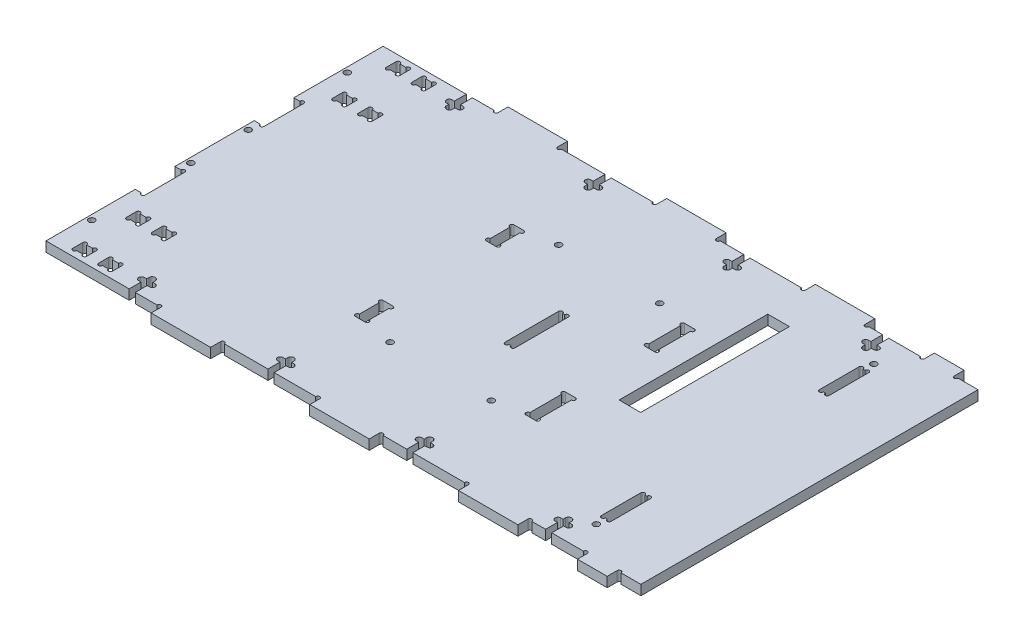
SolidWorks part; units mm, degrees
ref_plane "정면" through (0, 0, 0) normal (0, 0, 1) x (1, 0, 0)
ref_plane "윗면" through (0, 0, 0) normal (0, 1, 0) x (1, 0, 0)
ref_plane "우측면" through (0, 0, 0) normal (1, 0, 0) x (0, 0, -1)
sketch "스케치1" plane through (0, 0, 0) normal (0, 1, 0) x (1, 0, 0)
  line L1 (0, 0) -> (300, 0)
  line L2 (0, 0) -> (0, 170)
  line L3 (0, 170) -> (300, 170)
  line L4 (300, 0) -> (300, 170)
  dimension "D1" = 170
  dimension "D2" = 300
extrude "보스-돌출1" add sketch "스케치1" along normal blind 5
sketch "스케치2" plane through (0, 0, 0) normal (0, -1, 0) x (1, 0, 0)
  line L0 (160, -71.5) -> (160, 0) construction
  line L1 (160, -71.5) -> (165, -71.5)
  line L2 (160, -71.5) -> (160, -98.5)
  line L3 (160, -98.5) -> (165, -98.5)
  line L4 (165, -71.5) -> (165, -98.5)
  line L5 (0, 0) -> (300, 0) construction
  line L6 (160, -98.5) -> (160, -170) construction
  line L7 (300, -170) -> (0, -170) construction
  line L10 (300, 0) -> (300, -170) construction
  line L11 (260, 0) -> (260, -20) construction
  line L12 (260, -20) -> (265, -20)
  line L13 (260, -20) -> (260, -40)
  line L14 (260, -40) -> (265, -40)
  line L15 (265, -20) -> (265, -40)
  line L16 (260, -130) -> (265, -130)
  line L17 (260, -130) -> (260, -150)
  line L18 (260, -150) -> (265, -150)
  line L19 (265, -130) -> (265, -150)
  line L20 (260, -40) -> (260, -130) construction
  line L21 (260, -150) -> (260, -170) construction
  line L22 (265, -130) -> (265, -40) construction
  dimension "D1" = 27
  dimension "D2" = 140
  dimension "D3" = 5
  dimension "D4" = 20
  dimension "D5" = 20
  dimension "D6" = 40
  dimension "D7" = 5
extrude "컷-돌출1" cut sketch "스케치2" against normal blind 10
sketch "스케치3" plane through (0, 5, 0) normal (0, 1, 0) x (1, 0, 0)
  line L0 (183.55, 42.5) -> (180.45, 42.5) construction
  line L1 (183.55, 40) -> (183.55, 45) construction
  line L2 (180.45, 40) -> (180.45, 45) construction
  line L3 (180.45, 42.5) -> (132.55, 42.5) construction
  line L4 (132.55, 40) -> (132.55, 45) construction
  line L5 (132.55, 42.5) -> (129.45, 42.5) construction
  line L6 (129.45, 40) -> (129.45, 45) construction
  line L7 (183.55, 127.5) -> (180.45, 127.5) construction
  line L8 (183.55, 125) -> (183.55, 130) construction
  line L9 (180.45, 125) -> (180.45, 130) construction
  line L10 (180.45, 127.5) -> (132.55, 127.5) construction
  line L11 (132.55, 125) -> (132.55, 130) construction
  line L12 (132.55, 127.5) -> (129.45, 127.5) construction
  line L13 (129.45, 125) -> (129.45, 130) construction
  line L15 (2.5, 101) -> (2.5, 97.9) construction
  line L17 (5, 101) -> (0, 101) construction
  line L18 (262.5, 16.55) -> (262.5, 13.45) construction
  line L19 (265, 16.55) -> (260, 16.55) construction
  line L20 (265, 13.45) -> (260, 13.45) construction
  line L25 (262.5, 156.55) -> (262.5, 153.45) construction
  line L26 (265, 156.55) -> (260, 156.55) construction
  line L27 (265, 153.45) -> (260, 153.45) construction
  line L28 (5, 97.9) -> (0, 97.9) construction
  line L31 (2.5, 151) -> (2.5, 147.9) construction
  line L34 (2.5, 22.1) -> (2.5, 19) construction
  line L35 (5, 22.1) -> (0, 22.1) construction
  line L36 (5, 19) -> (0, 19) construction
  line L37 (2.5, 72.1) -> (2.5, 69) construction
  line L38 (5, 72.1) -> (0, 72.1) construction
  line L39 (5, 69) -> (0, 69) construction
  line L40 (5, 151) -> (0, 151) construction
  line L41 (5, 147.9) -> (0, 147.9) construction
  circle A0 centre (131, 127.5) radius 1.55
  circle A1 centre (182, 127.5) radius 1.55
  circle A2 centre (182, 42.5) radius 1.55
  circle A3 centre (131, 42.5) radius 1.55
  circle A4 centre (2.5, 70.55) radius 1.55
  circle A5 centre (2.5, 20.55) radius 1.55
  circle A6 centre (2.5, 99.45) radius 1.55
  circle A7 centre (2.5, 149.45) radius 1.55
  circle A8 centre (262.5, 155) radius 1.55
  circle A10 centre (262.5, 15) radius 1.55
  dimension "D1" = 3.1
extrude "컷-돌출2" cut sketch "스케치3" against normal blind 10
sketch "스케치4" plane through (0, 0, 0) normal (0, -1, 0) x (1, 0, 0)
  line L1 (0, -125) -> (5, -125)
  line L2 (0, -125) -> (0, -105)
  line L3 (0, -105) -> (5, -105)
  line L4 (5, -125) -> (5, -105)
  line L5 (0, -65) -> (5, -65)
  line L6 (0, -65) -> (0, -45)
  line L7 (0, -45) -> (5, -45)
  line L8 (5, -65) -> (5, -45)
extrude "컷-돌출3" cut sketch "스케치4" against normal blind 5
sketch "스케치5" plane through (0, 0, 0) normal (0, -1, 0) x (1, 0, 0)
  line L2 (5, -45) -> (0, -45) construction
  line L3 (0, -65) -> (5, -65) construction
  line L4 (5, -105) -> (0, -105) construction
  line L5 (0, -125) -> (5, -125) construction
  line L6 (160, -98.5) -> (165, -98.5) construction
  line L7 (165, -71.5) -> (160, -71.5) construction
  line L8 (265, -20) -> (260, -20) construction
  line L9 (260, -40) -> (265, -40) construction
  line L10 (265, -130) -> (260, -130) construction
  line L11 (260, -150) -> (265, -150) construction
  circle A1 centre (4, -45) radius 1
  circle A2 centre (4, -65) radius 1
  circle A5 centre (4, -105) radius 1
  circle A6 centre (4, -125) radius 1
  circle A8 centre (164, -98.5) radius 1
  circle A9 centre (161, -98.5) radius 1
  circle A10 centre (164, -71.5) radius 1
  circle A11 centre (161, -71.5) radius 1
  circle A12 centre (264, -20) radius 1
  circle A13 centre (261, -20) radius 1
  circle A14 centre (264, -40) radius 1
  circle A15 centre (261, -40) radius 1
  circle A16 centre (264, -130) radius 1
  circle A17 centre (261, -130) radius 1
  circle A18 centre (264, -150) radius 1
  circle A19 centre (261, -150) radius 1
  dimension "D1" = 2
extrude "컷-돌출4" cut sketch "스케치5" against normal blind 10
sketch "스케치8" plane through (0, 0, 0) normal (0, -1, 0) x (1, 0, 0)
  line L0 (0, 0) -> (300, 0) construction
  line L1 (58, 0) -> (88, 0)
  line L2 (58, 0) -> (58, 5)
  line L3 (58, 5) -> (88, 5)
  line L4 (88, 0) -> (88, 5)
  line L5 (0, 5) -> (58, 5) construction
  line L6 (0, 0) -> (300, 0) construction
  line L7 (138, 5) -> (168, 5)
  line L8 (138, 5) -> (138, 0)
  line L9 (138, 0) -> (168, 0)
  line L10 (168, 5) -> (168, 0)
  line L11 (0, 0) -> (300, 0) construction
  line L12 (213, 5) -> (243, 5)
  line L13 (213, 5) -> (213, 0)
  line L14 (213, 0) -> (243, 0)
  line L15 (243, 5) -> (243, 0)
  line L16 (0, 0) -> (300, 0) construction
  line L17 (273, 5) -> (288, 5)
  line L18 (273, 5) -> (273, 0)
  line L19 (273, 0) -> (288, 0)
  line L20 (288, 5) -> (288, 0)
  line L21 (300, 0) -> (300, -170) construction
  line L22 (0, -85) -> (300, -85) construction
  line L23 (0, -105) -> (0, -65) construction
  line L24 (288, -175) -> (288, -170)
  line L25 (273, -170) -> (288, -170)
  line L26 (273, -175) -> (273, -170)
  line L27 (273, -175) -> (288, -175)
  line L28 (243, -175) -> (243, -170)
  line L29 (213, -170) -> (243, -170)
  line L30 (213, -175) -> (213, -170)
  line L31 (213, -175) -> (243, -175)
  line L32 (168, -175) -> (168, -170)
  line L33 (138, -170) -> (168, -170)
  line L34 (138, -175) -> (138, -170)
  line L35 (138, -175) -> (168, -175)
  line L36 (88, -170) -> (88, -175)
  line L37 (58, -175) -> (88, -175)
  line L38 (58, -170) -> (58, -175)
  line L39 (58, -170) -> (88, -170)
  dimension "D1" = 12
  dimension "D2" = 15
  dimension "D3" = 30
  dimension "D4" = 30
  dimension "D5" = 45
  dimension "D6" = 30
  dimension "D7" = 50
  dimension "D8" = 30
extrude "보스-돌출2" add sketch "스케치8" against normal blind 5
sketch "스케치9" plane through (0, 0, 0) normal (0, -1, 0) x (1, 0, 0)
  line L0 (0, 0) -> (58, 0) construction
  line L1 (88, 0) -> (138, 0) construction
  line L2 (88, 0) -> (138, 0) construction
  line L3 (168, 0) -> (213, 0) construction
  line L4 (168, 0) -> (213, 0) construction
  line L5 (243, 0) -> (273, 0) construction
  line L6 (243, 0) -> (273, 0) construction
  line L7 (288, 0) -> (300, 0) construction
  line L8 (0, -85) -> (300, -85) construction
  line L9 (0, -105) -> (0, -65) construction
  line L10 (300, 0) -> (300, -170) construction
  circle A0 centre (57, 0) radius 1
  circle A1 centre (89, 0) radius 1
  circle A2 centre (137, 0) radius 1
  circle A3 centre (169, 0) radius 1
  circle A4 centre (212, 0) radius 1
  circle A5 centre (272, 0) radius 1
  circle A6 centre (244, 0) radius 1
  circle A7 centre (289, 0) radius 1
  circle A8 centre (289, -170) radius 1
  circle A9 centre (244, -170) radius 1
  circle A10 centre (272, -170) radius 1
  circle A11 centre (212, -170) radius 1
  circle A12 centre (169, -170) radius 1
  circle A13 centre (137, -170) radius 1
  circle A14 centre (89, -170) radius 1
  circle A15 centre (57, -170) radius 1
  dimension "D1" = 2
extrude "컷-돌출6" cut sketch "스케치9" against normal blind 5
sketch "스케치13" plane through (0, 5, 0) normal (0, 1, 0) x (1, 0, 0)
  line L0 (30, 8.5) -> (30, 30.5) construction
  line L1 (30, 8.5) -> (23, 8.5)
  line L2 (30, 8.5) -> (30, 3.5)
  line L3 (30, 3.5) -> (23, 3.5)
  line L4 (23, 8.5) -> (23, 3.5)
  line L5 (17, 8.5) -> (10, 8.5)
  line L6 (17, 8.5) -> (17, 3.5)
  line L7 (17, 3.5) -> (10, 3.5)
  line L8 (10, 8.5) -> (10, 3.5)
  line L9 (30, 19.5) -> (11.9274, 19.5) construction
  line L10 (10, 30.5) -> (10, 35.5)
  line L11 (17, 35.5) -> (10, 35.5)
  line L12 (17, 30.5) -> (17, 35.5)
  line L13 (17, 30.5) -> (10, 30.5)
  line L14 (23, 30.5) -> (23, 35.5)
  line L15 (30, 35.5) -> (23, 35.5)
  line L16 (30, 30.5) -> (30, 35.5)
  line L17 (30, 30.5) -> (23, 30.5)
  line L18 (0, 85) -> (49.672, 85) construction
  line L19 (0, 105) -> (0, 65) construction
  line L20 (30, 150.5) -> (11.9274, 150.5) construction
  line L21 (30, 161.5) -> (30, 139.5) construction
  line L22 (30, 139.5) -> (23, 139.5)
  line L23 (30, 139.5) -> (30, 134.5)
  line L24 (30, 134.5) -> (23, 134.5)
  line L25 (23, 139.5) -> (23, 134.5)
  line L26 (17, 139.5) -> (10, 139.5)
  line L27 (17, 139.5) -> (17, 134.5)
  line L28 (17, 134.5) -> (10, 134.5)
  line L29 (10, 139.5) -> (10, 134.5)
  line L30 (10, 161.5) -> (10, 166.5)
  line L31 (17, 166.5) -> (10, 166.5)
  line L32 (17, 161.5) -> (17, 166.5)
  line L33 (17, 161.5) -> (10, 161.5)
  line L34 (23, 161.5) -> (23, 166.5)
  line L35 (30, 166.5) -> (23, 166.5)
  line L36 (30, 161.5) -> (30, 166.5)
  line L37 (30, 161.5) -> (23, 161.5)
extrude "컷-돌출9" cut sketch "스케치13" against normal blind 10
sketch "스케치14" plane through (0, 0, 0) normal (0, -1, 0) x (1, 0, 0)
  line L0 (10, -8.5) -> (17, -8.5) construction
  line L1 (17, -3.5) -> (10, -3.5) construction
  line L2 (17, -30.5) -> (23, -30.5) construction
  line L3 (23, -30.5) -> (23, -8.5) construction
  line L4 (23, -8.5) -> (17, -8.5) construction
  line L5 (17, -8.5) -> (17, -30.5) construction
  line L6 (20, -30.5) -> (20, -8.5) construction
  line L7 (17, -19.5) -> (23, -19.5) construction
  line L8 (0, -85) -> (55.1733, -85) construction
  line L9 (0, -105) -> (0, -65) construction
  line L10 (17, -150.5) -> (23, -150.5) construction
  line L11 (20, -139.5) -> (20, -161.5) construction
  line L12 (17, -161.5) -> (17, -139.5) construction
  line L13 (23, -161.5) -> (17, -161.5) construction
  line L14 (23, -139.5) -> (23, -161.5) construction
  line L15 (17, -139.5) -> (23, -139.5) construction
  circle A0 centre (11, -8.5) radius 1
  circle A1 centre (11, -3.5) radius 1
  circle A2 centre (16, -3.5) radius 1
  circle A3 centre (16, -8.5) radius 1
  circle A4 centre (24, -8.5) radius 1
  circle A5 centre (24, -3.5) radius 1
  circle A6 centre (29, -3.5) radius 1
  circle A7 centre (29, -8.5) radius 1
  circle A8 centre (29, -30.5) radius 1
  circle A9 centre (29, -35.5) radius 1
  circle A10 centre (24, -35.5) radius 1
  circle A11 centre (24, -30.5) radius 1
  circle A12 centre (16, -30.5) radius 1
  circle A13 centre (16, -35.5) radius 1
  circle A14 centre (11, -35.5) radius 1
  circle A15 centre (11, -30.5) radius 1
  circle A16 centre (11, -139.5) radius 1
  circle A17 centre (11, -134.5) radius 1
  circle A18 centre (16, -134.5) radius 1
  circle A19 centre (16, -139.5) radius 1
  circle A20 centre (24, -139.5) radius 1
  circle A21 centre (24, -134.5) radius 1
  circle A22 centre (29, -134.5) radius 1
  circle A23 centre (29, -139.5) radius 1
  circle A24 centre (29, -161.5) radius 1
  circle A25 centre (29, -166.5) radius 1
  circle A26 centre (24, -166.5) radius 1
  circle A27 centre (24, -161.5) radius 1
  circle A28 centre (16, -161.5) radius 1
  circle A29 centre (16, -166.5) radius 1
  circle A30 centre (11, -166.5) radius 1
  circle A31 centre (11, -161.5) radius 1
  dimension "D1" = 2
extrude "컷-돌출10" cut sketch "스케치14" against normal blind 10
sketch "스케치15" plane through (0, 5, 0) normal (0, 1, 0) x (1, 0, 0)
  line L1 (111, 125) -> (116, 125)
  line L2 (111, 125) -> (111, 111)
  line L3 (111, 111) -> (116, 111)
  line L4 (116, 125) -> (116, 111)
  line L5 (111, 45) -> (116, 45)
  line L6 (111, 45) -> (111, 59)
  line L7 (111, 59) -> (116, 59)
  line L8 (116, 45) -> (116, 59)
  line L9 (197, 65) -> (202, 65)
  line L10 (197, 65) -> (197, 45)
  line L11 (197, 45) -> (202, 45)
  line L12 (202, 65) -> (202, 45)
  line L13 (197, 105) -> (202, 105)
  line L14 (197, 105) -> (197, 125)
  line L15 (197, 125) -> (202, 125)
  line L16 (202, 105) -> (202, 125)
  arc A0 (116, 56.5) -> (116, 59) centre (116, 57.75) ccw construction
  dimension "D1" = 5
extrude "컷-돌출11" cut sketch "스케치15" against normal blind 10
sketch "스케치16" plane through (0, 5, 0) normal (0, 1, 0) x (1, 0, 0)
  line L0 (111, 59) -> (111, 45) construction
  line L1 (116, 45) -> (116, 59) construction
  line L2 (111, 125) -> (111, 111) construction
  line L3 (116, 111) -> (116, 125) construction
  line L4 (202, 105) -> (202, 125) construction
  line L5 (197, 125) -> (197, 105) construction
  line L6 (197, 65) -> (197, 45) construction
  line L7 (202, 45) -> (202, 65) construction
  circle A0 centre (111, 46) radius 1
  circle A1 centre (116, 46) radius 1
  circle A2 centre (116, 58) radius 1
  circle A3 centre (111, 58) radius 1
  circle A4 centre (111, 112) radius 1
  circle A5 centre (116, 112) radius 1
  circle A6 centre (116, 124) radius 1
  circle A7 centre (111, 124) radius 1
  circle A8 centre (202, 124) radius 1
  circle A10 centre (197, 124) radius 1
  circle A11 centre (197, 64) radius 1
  circle A12 centre (202, 64) radius 1
  circle A13 centre (202, 106) radius 1
  circle A14 centre (197, 106) radius 1
  circle A15 centre (197, 46) radius 1
  circle A16 centre (202, 46) radius 1
  dimension "D1" = 2
extrude "컷-돌출12" cut sketch "스케치16" against normal blind 10
sketch "스케치17" plane through (0, 5, 0) normal (0, 1, 0) x (1, 0, 0)
  line L0 (219, 97.5569) -> (219, 95.1974) construction
  line L1 (214, 75) -> (224.9, 75)
  line L2 (214, 75) -> (214, 150)
  line L3 (214, 150) -> (224.9, 150)
  line L4 (224.9, 75) -> (224.9, 150)
  line L6 (219.9, 97.5569) -> (219.9, 95.1974) construction
  line L7 (0, -5) -> (300, -5) construction
  line L8 (211, 170) -> (170, 170) construction
  dimension "D1" = 5
  dimension "D2" = 5
  dimension "D3" = 80
  dimension "D4" = 20
extrude "컷-돌출13" cut sketch "스케치17" against normal blind 10
sketch "스케치7" plane through (0, 0, 0) normal (0, -1, 0) x (1, 0, 0)
  line L0 (115.0287, -170) -> (111.9287, -170)
  line L1 (115.0287, -164) -> (116.2287, -164)
  line L2 (115.0287, -161.2) -> (115.0287, -160)
  line L3 (111.9287, -161.2) -> (111.9287, -160)
  line L4 (111.9287, -161.2) -> (110.7287, -161.2)
  line L5 (111.9287, -170) -> (111.9287, -164)
  line L6 (110.7287, -164) -> (111.9287, -164)
  line L7 (115.0287, -170) -> (115.0287, -164)
  line L8 (116.2287, -161.2) -> (115.0287, -161.2)
  line L9 (115.0287, -161.2) -> (111.9287, -161.2) construction
  line L10 (115.0287, -161.2) -> (115.0287, -164) construction
  line L11 (111.9287, -164) -> (111.9287, -161.2) construction
  line L12 (115.0287, -160) -> (111.9287, -160) construction
  line L13 (113.4787, -160) -> (113.4787, -157.529) construction
  line L14 (110.7287, -161.2) -> (110.7287, -164) construction
  line L15 (116.2287, -164) -> (116.2287, -161.2) construction
  line L16 (115.0287, -164) -> (111.9287, -164) construction
  line L17 (185.0287, -170) -> (181.9287, -170)
  line L18 (185.0287, -164) -> (186.2287, -164)
  line L19 (185.0287, -161.2) -> (185.0287, -160)
  line L20 (181.9287, -161.2) -> (181.9287, -160)
  line L21 (181.9287, -161.2) -> (180.7287, -161.2)
  line L22 (181.9287, -170) -> (181.9287, -164)
  line L23 (180.7287, -164) -> (181.9287, -164)
  line L24 (185.0287, -170) -> (185.0287, -164)
  line L25 (186.2287, -161.2) -> (185.0287, -161.2)
  line L26 (185.0287, -161.2) -> (181.9287, -161.2) construction
  line L27 (185.0287, -161.2) -> (185.0287, -164) construction
  line L28 (181.9287, -164) -> (181.9287, -161.2) construction
  line L29 (185.0287, -160) -> (181.9287, -160) construction
  line L30 (45.0287, -161.2) -> (41.9287, -161.2) construction
  line L31 (45.0287, -161.2) -> (45.0287, -164) construction
  line L32 (41.9287, -164) -> (41.9287, -161.2) construction
  line L33 (45.0287, -160) -> (41.9287, -160) construction
  line L34 (43.4787, -160) -> (43.4787, -157.529) construction
  line L35 (183.4787, -160) -> (183.4787, -157.529) construction
  line L36 (180.7287, -161.2) -> (180.7287, -164) construction
  line L37 (186.2287, -164) -> (186.2287, -161.2) construction
  line L38 (185.0287, -164) -> (181.9287, -164) construction
  line L39 (255.0287, -170) -> (251.9287, -170)
  line L40 (255.0287, -164) -> (256.2287, -164)
  line L41 (255.0287, -161.2) -> (255.0287, -160)
  line L42 (251.9287, -161.2) -> (251.9287, -160)
  line L43 (251.9287, -161.2) -> (250.7287, -161.2)
  line L44 (251.9287, -170) -> (251.9287, -164)
  line L45 (250.7287, -164) -> (251.9287, -164)
  line L46 (255.0287, -170) -> (255.0287, -164)
  line L47 (256.2287, -161.2) -> (255.0287, -161.2)
  line L48 (255.0287, -161.2) -> (251.9287, -161.2) construction
  line L49 (255.0287, -161.2) -> (255.0287, -164) construction
  line L50 (251.9287, -164) -> (251.9287, -161.2) construction
  line L51 (255.0287, -160) -> (251.9287, -160) construction
  line L52 (253.4787, -160) -> (253.4787, -157.529) construction
  line L53 (250.7287, -161.2) -> (250.7287, -164) construction
  line L54 (256.2287, -164) -> (256.2287, -161.2) construction
  line L55 (255.0287, -164) -> (251.9287, -164) construction
  line L56 (45.0287, -6) -> (41.9287, -6) construction
  line L57 (46.2287, -6) -> (46.2287, -8.8) construction
  line L58 (40.7287, -8.8) -> (40.7287, -6) construction
  line L59 (255.0287, -6) -> (251.9287, -6) construction
  line L60 (256.2287, -6) -> (256.2287, -8.8) construction
  line L61 (250.7287, -8.8) -> (250.7287, -6) construction
  line L62 (253.4787, -10) -> (253.4787, -12.471) construction
  line L63 (255.0287, -10) -> (251.9287, -10) construction
  line L64 (251.9287, -6) -> (251.9287, -8.8) construction
  line L65 (255.0287, -8.8) -> (255.0287, -6) construction
  line L66 (255.0287, -8.8) -> (251.9287, -8.8) construction
  line L67 (185.0287, -6) -> (181.9287, -6) construction
  line L68 (186.2287, -6) -> (186.2287, -8.8) construction
  line L69 (40.7287, -161.2) -> (40.7287, -164) construction
  line L71 (180.7287, -8.8) -> (180.7287, -6) construction
  line L72 (183.4787, -10) -> (183.4787, -12.471) construction
  line L73 (43.4787, -10) -> (43.4787, -12.471) construction
  line L74 (45.0287, -10) -> (41.9287, -10) construction
  line L75 (0, -85) -> (300, -85) construction
  line L76 (0, -105) -> (0, -65) construction
  line L77 (300, 0) -> (300, -170) construction
  line L78 (46.2287, -164) -> (46.2287, -161.2) construction
  line L79 (45.0287, -164) -> (41.9287, -164) construction
  line L80 (41.9287, -6) -> (41.9287, -8.8) construction
  line L81 (45.0287, -8.8) -> (45.0287, -6) construction
  line L82 (45.0287, -8.8) -> (41.9287, -8.8) construction
  line L83 (185.0287, -10) -> (181.9287, -10) construction
  line L84 (181.9287, -6) -> (181.9287, -8.8) construction
  line L85 (185.0287, -8.8) -> (185.0287, -6) construction
  line L86 (185.0287, -8.8) -> (181.9287, -8.8) construction
  line L87 (115.0287, -6) -> (111.9287, -6) construction
  line L88 (116.2287, -6) -> (116.2287, -8.8) construction
  line L89 (110.7287, -8.8) -> (110.7287, -6) construction
  line L90 (113.4787, -10) -> (113.4787, -12.471) construction
  line L91 (115.0287, -10) -> (111.9287, -10) construction
  line L92 (111.9287, -6) -> (111.9287, -8.8) construction
  line L93 (115.0287, -8.8) -> (115.0287, -6) construction
  line L94 (115.0287, -8.8) -> (111.9287, -8.8) construction
  line L95 (46.2287, -8.8) -> (45.0287, -8.8)
  line L96 (45.0287, 0) -> (45.0287, -6)
  line L97 (45.0287, -170) -> (41.9287, -170)
  line L98 (45.0287, -164) -> (46.2287, -164)
  line L99 (45.0287, -161.2) -> (45.0287, -160)
  line L100 (41.9287, -161.2) -> (41.9287, -160)
  line L101 (41.9287, -161.2) -> (40.7287, -161.2)
  line L102 (41.9287, -170) -> (41.9287, -164)
  line L103 (40.7287, -164) -> (41.9287, -164)
  line L104 (45.0287, -170) -> (45.0287, -164)
  line L105 (46.2287, -161.2) -> (45.0287, -161.2)
  line L106 (325.0287, -170) -> (321.9287, -170) [skipped]
  line L107 (325.0287, -164) -> (326.2287, -164) [skipped]
  line L108 (325.0287, -161.2) -> (325.0287, -160) [skipped]
  line L109 (321.9287, -161.2) -> (321.9287, -160) [skipped]
  line L110 (321.9287, -161.2) -> (320.7287, -161.2) [skipped]
  line L111 (321.9287, -170) -> (321.9287, -164) [skipped]
  line L112 (320.7287, -164) -> (321.9287, -164) [skipped]
  line L113 (325.0287, -170) -> (325.0287, -164) [skipped]
  line L114 (326.2287, -161.2) -> (325.0287, -161.2) [skipped]
  line L115 (325.0287, -161.2) -> (321.9287, -161.2) construction
  line L116 (325.0287, -161.2) -> (325.0287, -164) construction
  line L117 (321.9287, -164) -> (321.9287, -161.2) construction
  line L118 (325.0287, -160) -> (321.9287, -160) construction
  line L119 (323.4787, -160) -> (323.4787, -157.529) construction
  line L120 (320.7287, -161.2) -> (320.7287, -164) construction
  line L121 (326.2287, -164) -> (326.2287, -161.2) construction
  line L122 (325.0287, -164) -> (321.9287, -164) construction
  line L123 (40.7287, -6) -> (41.9287, -6)
  line L124 (41.9287, 0) -> (41.9287, -6)
  line L125 (41.9287, -8.8) -> (40.7287, -8.8)
  line L126 (41.9287, -8.8) -> (41.9287, -10)
  line L127 (45.0287, -8.8) -> (45.0287, -10)
  line L128 (45.0287, -6) -> (46.2287, -6)
  line L129 (45.0287, 0) -> (41.9287, 0)
  line L130 (256.2287, -8.8) -> (255.0287, -8.8)
  line L131 (255.0287, 0) -> (255.0287, -6)
  line L132 (250.7287, -6) -> (251.9287, -6)
  line L133 (251.9287, 0) -> (251.9287, -6)
  line L134 (251.9287, -8.8) -> (250.7287, -8.8)
  line L135 (251.9287, -8.8) -> (251.9287, -10)
  line L136 (255.0287, -8.8) -> (255.0287, -10)
  line L137 (255.0287, -6) -> (256.2287, -6)
  line L138 (255.0287, 0) -> (251.9287, 0)
  line L139 (186.2287, -8.8) -> (185.0287, -8.8)
  line L140 (185.0287, 0) -> (185.0287, -6)
  line L141 (180.7287, -6) -> (181.9287, -6)
  line L142 (181.9287, 0) -> (181.9287, -6)
  line L143 (181.9287, -8.8) -> (180.7287, -8.8)
  line L144 (181.9287, -8.8) -> (181.9287, -10)
  line L145 (185.0287, -8.8) -> (185.0287, -10)
  line L146 (185.0287, -6) -> (186.2287, -6)
  line L147 (185.0287, 0) -> (181.9287, 0)
  line L148 (116.2287, -8.8) -> (115.0287, -8.8)
  line L149 (115.0287, 0) -> (115.0287, -6)
  line L150 (110.7287, -6) -> (111.9287, -6)
  line L151 (111.9287, 0) -> (111.9287, -6)
  line L152 (111.9287, -8.8) -> (110.7287, -8.8)
  line L153 (111.9287, -8.8) -> (111.9287, -10)
  line L154 (115.0287, -8.8) -> (115.0287, -10)
  line L155 (115.0287, -6) -> (116.2287, -6)
  line L156 (115.0287, 0) -> (111.9287, 0)
  arc A0 (111.9287, -160) -> (115.0287, -160) centre (113.4787, -160) cw
  arc A1 (116.2287, -161.2) -> (116.2287, -164) centre (116.2287, -162.6) cw
  arc A2 (110.7287, -164) -> (110.7287, -161.2) centre (110.7287, -162.6) cw
  arc A3 (181.9287, -160) -> (185.0287, -160) centre (183.4787, -160) cw
  arc A4 (186.2287, -161.2) -> (186.2287, -164) centre (186.2287, -162.6) cw
  arc A5 (180.7287, -164) -> (180.7287, -161.2) centre (180.7287, -162.6) cw
  arc A6 (251.9287, -160) -> (255.0287, -160) centre (253.4787, -160) cw
  arc A7 (256.2287, -161.2) -> (256.2287, -164) centre (256.2287, -162.6) cw
  arc A8 (250.7287, -164) -> (250.7287, -161.2) centre (250.7287, -162.6) cw
  arc A9 (40.7287, -6) -> (40.7287, -8.8) centre (40.7287, -7.4) ccw
  arc A10 (46.2287, -8.8) -> (46.2287, -6) centre (46.2287, -7.4) ccw
  arc A11 (41.9287, -10) -> (45.0287, -10) centre (43.4787, -10) ccw
  arc A12 (250.7287, -6) -> (250.7287, -8.8) centre (250.7287, -7.4) ccw
  arc A13 (41.9287, -160) -> (45.0287, -160) centre (43.4787, -160) cw
  arc A14 (46.2287, -161.2) -> (46.2287, -164) centre (46.2287, -162.6) cw
  arc A15 (40.7287, -164) -> (40.7287, -161.2) centre (40.7287, -162.6) cw
  arc A16 (321.9287, -160) -> (325.0287, -160) centre (323.4787, -160) cw [skipped]
  arc A17 (326.2287, -161.2) -> (326.2287, -164) centre (326.2287, -162.6) cw [skipped]
  arc A18 (320.7287, -164) -> (320.7287, -161.2) centre (320.7287, -162.6) cw [skipped]
  arc A19 (256.2287, -8.8) -> (256.2287, -6) centre (256.2287, -7.4) ccw
  arc A20 (251.9287, -10) -> (255.0287, -10) centre (253.4787, -10) ccw
  arc A21 (180.7287, -6) -> (180.7287, -8.8) centre (180.7287, -7.4) ccw
  arc A22 (186.2287, -8.8) -> (186.2287, -6) centre (186.2287, -7.4) ccw
  arc A23 (181.9287, -10) -> (185.0287, -10) centre (183.4787, -10) ccw
  arc A24 (110.7287, -6) -> (110.7287, -8.8) centre (110.7287, -7.4) ccw
  arc A25 (116.2287, -8.8) -> (116.2287, -6) centre (116.2287, -7.4) ccw
  arc A26 (111.9287, -10) -> (115.0287, -10) centre (113.4787, -10) ccw
  dimension "D1" = 5
extrude "컷-돌출5" cut sketch "스케치7" against normal blind 10
